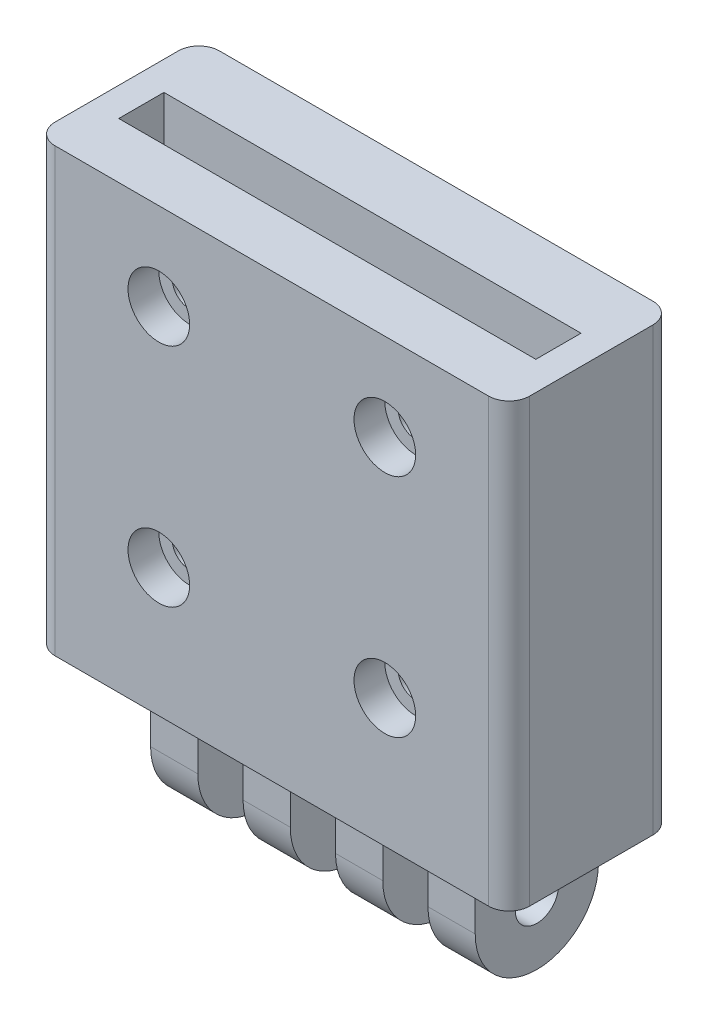
SolidWorks part; units mm, degrees
ref_plane "Front Plane" through (0, 0, 0) normal (0, 0, 1) x (1, 0, 0)
ref_plane "Top Plane" through (0, 0, 0) normal (0, 1, 0) x (1, 0, 0)
ref_plane "Right Plane" through (0, 0, 0) normal (1, 0, 0) x (0, 0, -1)
sketch "Sketch1" plane through (0, 0, 0) normal (0, 1, 0) x (1, 0, 0)
  line L1 (23.1, 8) -> (-23.1, 8)
  line L2 (23.1, 8) -> (23.1, -8)
  line L3 (23.1, -8) -> (-23.1, -8)
  line L4 (-23.1, 8) -> (-23.1, -8)
  line L5 (23.1, 8) -> (-23.1, -8) construction
  line L6 (23.1, -8) -> (-23.1, 8) construction
  point P0 (0, 0)
  dimension "D1" = 16
  dimension "D2" = 46.2
extrude "Boss-Extrude1" add sketch "Sketch1" along normal blind 43
sketch "Sketch2" plane through (0, 0, 0) normal (0, -1, 0) x (1, 0, 0)
  line L0 (23.1, -8) -> (-23.1, -8) construction
  line L1 (15.8, -8) -> (11.2, -8)
  line L2 (15.8, -8) -> (15.8, 4)
  line L3 (15.8, 4) -> (11.2, 4)
  line L4 (11.2, -8) -> (11.2, 4)
  line L5 (13.5, 8) -> (13.5, -8) construction
  line L6 (15.8, -2) -> (11.2, -2) construction
  point P272 (13.5, -2)
  dimension "D1" = 12
  dimension "D2" = 4.6
extrude "Boss-Extrude2" add sketch "Sketch2" along normal blind 7
sketch "Sketch8" plane through (15.8, 0, 0) normal (1, 0, 0) x (0, 0, -1)
  line L0 (8, -7) -> (-4, -7) construction
  line L1 (8, -7) -> (8, 0) construction
  circle A0 centre (2, -7) radius 6
  dimension "D1" = 12
extrude "Boss-Extrude3" add sketch "Sketch8" against normal up to surface (4.6 mm away) up to face at (11.2, -3.5, -2)
pattern_linear "LPattern1" count 4 spacing 9 along (-1, 0, 0) of "Boss-Extrude2", "Boss-Extrude3"
sketch "Sketch4" plane through (15.8, 0, 0) normal (1, 0, 0) x (0, 0, -1)
  circle A0 centre (2, -7) radius 2.1
  arc A2 (-4, -7) -> (8, -7) centre (2, -7) ccw construction
  dimension "D1" = 4.2
  dimension "D2" = 0
extrude "Cut-Extrude1" cut sketch "Sketch4" against normal through all
sketch "Sketch6" plane through (0, 43, 0) normal (0, 1, 0) x (1, 0, 0)
  line L0 (-23.1, -8) -> (23.1, -8) construction
  line L1 (20.3, -2.6) -> (-20.3, -2.6)
  line L2 (20.3, -2.6) -> (20.3, 1.8)
  line L3 (20.3, 1.8) -> (-20.3, 1.8)
  line L4 (-20.3, -2.6) -> (-20.3, 1.8)
  line L5 (20.3, -2.6) -> (-20.3, 1.8) construction
  line L6 (20.3, 1.8) -> (-20.3, -2.6) construction
  line L7 (-23.1, 8) -> (-23.1, -8) construction
  line L9 (23.1, 8) -> (-23.1, 8) construction
  point P0 (0, -0.4)
  dimension "D1" = 5.4
  dimension "D2" = 2.8
  dimension "D3" = 6.2
extrude "Cut-Extrude2" cut sketch "Sketch6" against normal blind 40
sketch "Sketch9" plane through (0, 0, 8) normal (0, 0, 1) x (1, 0, 0)
  line L0 (20, 43) -> (20, 0) construction
  line L1 (-23.1, 43) -> (23.1, 43) construction
  line L2 (-23.1, 0) -> (23.1, 0) construction
  line L3 (-20, 43) -> (-20, 0) construction
  line L4 (-23.1, 0) -> (23.1, 0) construction
  line L5 (23.1, 3) -> (-23.1, 3) construction
  line L6 (23.1, 43) -> (23.1, 0) construction
  line L7 (-23.1, 43) -> (-23.1, 0) construction
  line L8 (0, 3) -> (0, 43) construction
  circle A0 centre (11, 12.5) radius 1.7
  circle A1 centre (-11, 12.5) radius 1.7
  circle A2 centre (11, 34.5) radius 1.7
  circle A3 centre (-11, 34.5) radius 1.7
  dimension "D8" = 3.4
  dimension "D1" = 40
  dimension "D2" = 40
  dimension "D3" = 9
  dimension "D4" = 8.5
  dimension "D5" = 9
  dimension "D6" = 9.5
  dimension "D7" = 20
extrude "Cut-Extrude3" cut sketch "Sketch9" against normal through all
fillet "Fillet2" radius 2 4 edges at (23.1, 21.5, -8) (-23.1, 21.5, -8) (-23.1, 21.5, 8) (23.1, 21.5, 8)
sketch "Sketch10" plane through (0, 0, -8) normal (0, 0, -1) x (-1, 0, 0)
  line L0 (12.5877, 9.75) -> (9.4123, 9.75)
  line L1 (9.4123, 9.75) -> (7.8246, 12.5)
  line L2 (7.8246, 12.5) -> (9.4123, 15.25)
  line L3 (9.4123, 15.25) -> (12.5877, 15.25)
  line L4 (12.5877, 15.25) -> (14.1754, 12.5)
  line L5 (14.1754, 12.5) -> (12.5877, 9.75)
  line L6 (12.5877, 9.75) -> (9.4123, 15.25) construction
  line L7 (14.1754, 12.5) -> (7.8246, 12.5) construction
  line L8 (12.5877, 15.25) -> (9.4123, 9.75) construction
  circle A0 centre (11, 12.5) radius 1.7 construction
  point P5 (11, 12.5)
  dimension "D1" = 60
  dimension "D2" = 5.5
extrude "Cut-Extrude4" cut sketch "Sketch10" against normal blind 4
pattern_linear "LPattern2" count 2 spacing 22 along (0, 1, 0) count 2 spacing 22 along (1, 0, 0) of "Cut-Extrude4"
sketch "Sketch11" plane through (0, 0, 8) normal (0, 0, 1) x (1, 0, 0)
  circle A2 centre (11, 12.5) radius 3
  circle A3 centre (-11, 12.5) radius 3
  circle A4 centre (-11, 34.5) radius 3
  circle A5 centre (11, 34.5) radius 3
  dimension "D1" = 6
extrude "Cut-Extrude5" cut sketch "Sketch11" against normal blind 3
